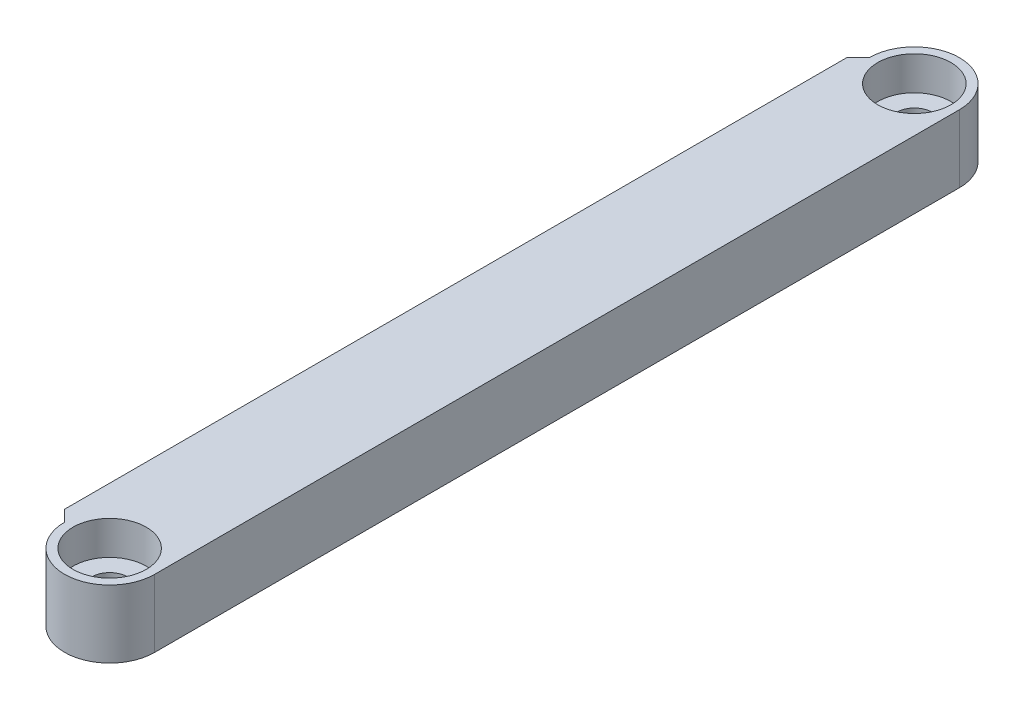
SolidWorks part; units mm, degrees
ref_plane "Спереди" through (0, 0, 0) normal (0, 0, 1) x (1, 0, 0)
ref_plane "Сверху" through (0, 0, 0) normal (0, 1, 0) x (1, 0, 0)
ref_plane "Справа" through (0, 0, 0) normal (1, 0, 0) x (0, 0, -1)
other "Configuration Table"
sketch "Эскиз1" plane through (0, 0, 0) normal (0, 1, 0) x (1, 0, 0)
  line L0 (-4, 0) -> (-5, 0)
  line L2 (4, 0) -> (4, -71.4)
  line L4 (-5, 0) -> (-5, -71.4)
  line L5 (-4, -71.4) -> (-5, -71.4)
  circle A0 centre (0, 0) radius 1.6
  circle A1 centre (0, -71.4) radius 1.6
  arc A2 (4, 0) -> (-4, 0) centre (0, 0) ccw
  arc A3 (-4, -71.4) -> (4, -71.4) centre (0, -71.4) ccw
  dimension "D1" = 3.2
  dimension "D2" = 3.2
  dimension "D4" = 8
  dimension "D5" = 8
  dimension "D3" = 71.4
  dimension "D6" = 5
extrude "Бобышка-Вытянуть1" add sketch "Эскиз1" along normal blind 6
chamfer "Фаска1" distance 1 angle 45 2 edges at (-5, 3, 0) (-5, 3, 71.4)
sketch "Эскиз2" plane through (0, 6, 0) normal (0, 1, 0) x (1, 0, 0)
  circle A0 centre (0, 0) radius 3.25
  circle A1 centre (0, -71.4) radius 3.25
  dimension "D1" = 6.5
  dimension "D2" = 6.5
extrude "Вырез-Вытянуть1" cut sketch "Эскиз2" against normal blind 3
